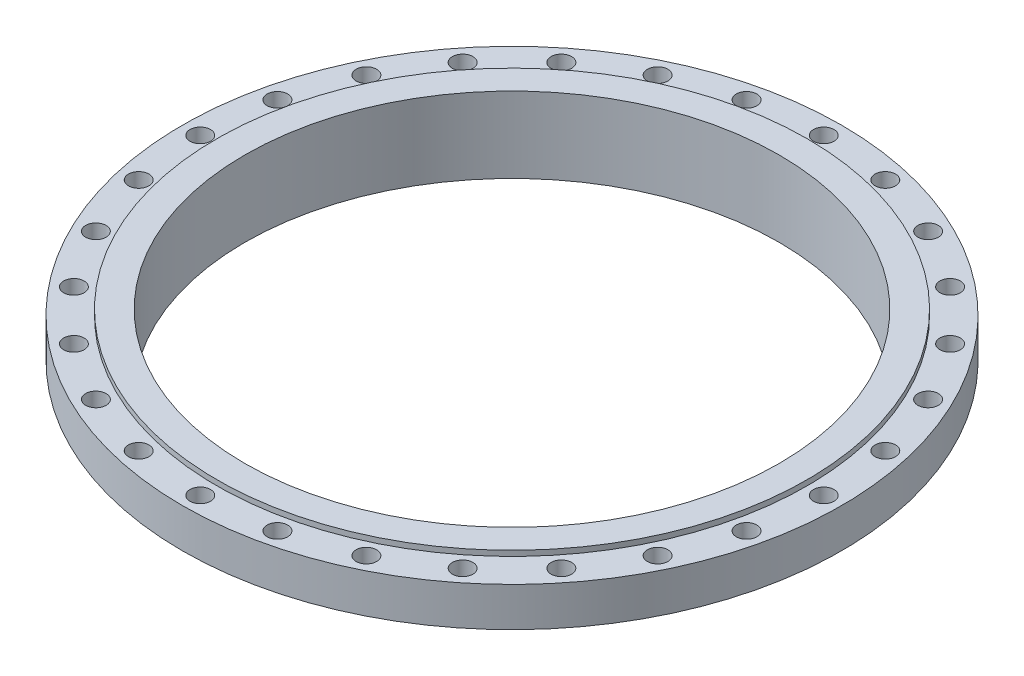
SolidWorks part; units mm, degrees
ref_plane "Спереди" through (0, 0, 0) normal (0, 0, 1) x (1, 0, 0)
ref_plane "Сверху" through (0, 0, 0) normal (0, 1, 0) x (1, 0, 0)
ref_plane "Справа" through (0, 0, 0) normal (1, 0, 0) x (0, 0, -1)
sketch "Эскиз1" plane through (0, 0, 0) normal (0, 0, 1) x (1, 0, 0)
  line L0 (0, 0) -> (0, 152.1529) construction
  line L1 (-300, 0) -> (-300, 35)
  line L2 (-300, 85) -> (-331.5, 85)
  line L3 (-331.5, 85) -> (-331.5, 79)
  line L4 (-300, 35) -> (0, 35)
  line L5 (0, 35) -> (0, 75)
  line L6 (-331.5, 79) -> (-370, 79)
  line L7 (-370, 79) -> (-370, 35)
  line L8 (-370, 35) -> (-329, 35)
  line L9 (-322.3784, 30.2703) -> (-312, 0)
  line L10 (-312, 0) -> (-300, 0)
  line L11 (0, 75) -> (-300, 75)
  line L12 (-300, 75) -> (-300, 85)
  arc A0 (-322.3784, 30.2703) -> (-329, 35) centre (-329, 28) ccw
  point P15 (-324, 35)
  dimension "D11" = 7
  dimension "D1" = 740
  dimension "D2" = 40
  dimension "D3" = 624
  dimension "D4" = 648
  dimension "D5" = 663
  dimension "D6" = 6
  dimension "D7" = 50
  dimension "D8" = 85
  dimension "D9" = 10
  dimension "D10" = 600
revolve "Повернуть1" add sketch "Эскиз1" angle 360 about L0
sketch "Эскиз2" plane through (0, 79, 0) normal (0, 1, 0) x (1, 0, 0)
  circle A0 centre (0, 0) radius 350 construction
  circle A1 centre (0, 350) radius 11.5
  circle A2 centre (77.8823, 341.2248) radius 11.5
  circle A3 centre (151.8593, 315.3391) radius 11.5
  circle A4 centre (218.2214, 273.641) radius 11.5
  circle A5 centre (273.641, 218.2214) radius 11.5
  circle A6 centre (315.3391, 151.8593) radius 11.5
  circle A7 centre (341.2248, 77.8823) radius 11.5
  circle A8 centre (350, 0) radius 11.5
  circle A9 centre (341.2248, -77.8823) radius 11.5
  circle A10 centre (315.3391, -151.8593) radius 11.5
  circle A11 centre (273.641, -218.2214) radius 11.5
  circle A12 centre (218.2214, -273.641) radius 11.5
  circle A13 centre (151.8593, -315.3391) radius 11.5
  circle A14 centre (77.8823, -341.2248) radius 11.5
  circle A15 centre (0, -350) radius 11.5
  circle A16 centre (-77.8823, -341.2248) radius 11.5
  circle A17 centre (-151.8593, -315.3391) radius 11.5
  circle A18 centre (-218.2214, -273.641) radius 11.5
  circle A19 centre (-273.641, -218.2214) radius 11.5
  circle A20 centre (-315.3391, -151.8593) radius 11.5
  circle A21 centre (-341.2248, -77.8823) radius 11.5
  circle A22 centre (-350, 0) radius 11.5
  circle A23 centre (-341.2248, 77.8823) radius 11.5
  circle A24 centre (-315.3391, 151.8593) radius 11.5
  circle A25 centre (-273.641, 218.2214) radius 11.5
  circle A26 centre (-218.2214, 273.641) radius 11.5
  circle A27 centre (-151.8593, 315.3391) radius 11.5
  circle A28 centre (-77.8823, 341.2248) radius 11.5
  point P61 (0, 0)
  dimension "D1" = 700
  dimension "D2" = 23
  dimension "D3" = 28
extrude "Вырез-Вытянуть1" cut sketch "Эскиз2" against normal through all
ref_axis "Ось1" through (-80.9, 0, 0) along (1, 0, 0)
ref_axis "Ось2" through (0, 0, -80.9) along (0, 0, 1)
sketch "Sketch1" plane through (0, 75, 0) normal (0, 1, 0) x (1, 0, 0)
  circle A0 centre (0, 0) radius 300
extrude "Cut-Extrude1" cut sketch "Sketch1" against normal through all
